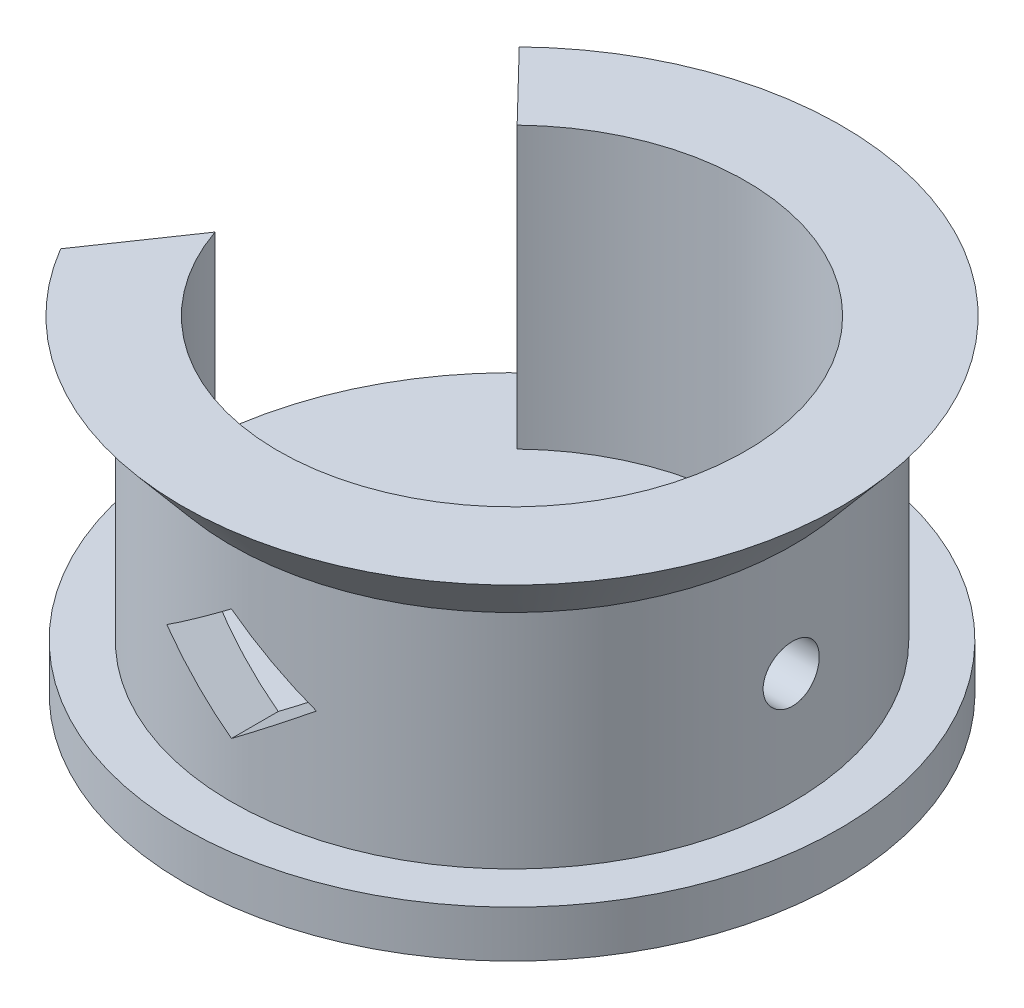
SolidWorks part; units mm, degrees
ref_plane "Front Plane" through (0, 0, 0) normal (0, 0, 1) x (1, 0, 0)
ref_plane "Top Plane" through (0, 0, 0) normal (0, 1, 0) x (1, 0, 0)
ref_plane "Right Plane" through (0, 0, 0) normal (1, 0, 0) x (0, 0, -1)
sketch "Sketch4" plane through (0, 0, 0) normal (0, 1, 0) x (1, 0, 0)
  circle A0 centre (0, 0) radius 7
extrude "Boss-Extrude3" add sketch "Sketch4" along normal blind 1
sketch "Sketch5" plane through (0, 1, 0) normal (0, 1, 0) x (1, 0, 0)
  circle A0 centre (0, 0) radius 6
  circle A1 centre (0, 0) radius 5
extrude "Boss-Extrude4" add sketch "Sketch5" along normal blind 4.75
sketch "Sketch6" plane through (0, 0, 0) normal (0, 0, 1) x (1, 0, 0)
  line L0 (0, 5.75) -> (6, 5.75)
  line L1 (5, 5.75) -> (-5, 5.75) construction
  line L7 (6, 7) -> (6, 5.75)
  line L8 (0, 7) -> (6, 7)
  line L10 (0, 5.75) -> (0, 7)
revolve "Revolve4" add sketch "Sketch6" angle 360 about L10
sketch "Sketch9" plane through (0, 7, 0) normal (0, 1, 0) x (1, 0, 0)
  circle A0 centre (0, 0) radius 5
extrude "Cut-Extrude3" cut sketch "Sketch9" against normal blind 3
sketch "Sketch11" plane through (0, 0, 0) normal (0, 0, 1) x (1, 0, 0)
  line L0 (0, 3.375) -> (0, 4.575)
  line L1 (0, 3.375) -> (0, 2.175)
  line L2 (0, 3.375) -> (-1.2, 3.375)
  line L3 (0, 3.375) -> (1.2, 3.375)
  line L5 (0, 2.175) -> (1.6, 3.375)
  line L6 (0, 4.575) -> (1.6, 3.375)
  line L7 (0, 3.375) -> (-1.6, 3.375)
  line L8 (-1.6, 3.375) -> (0, 4.575)
  line L9 (-1.6, 3.375) -> (0, 2.175)
  line L15 (0, 3.375) -> (1.6, 3.375)
extrude "Cut-Extrude7" cut sketch "Sketch11" along normal blind 10 contours L3 L15 L6 L0 | L8 L7 L2 L0 | L7 L9 L1 L2 | L15 L3 L1 L5 region at (-0.5333, 3.775, 0) region at (0.5333, 2.975, 0) region at (-0.5333, 2.975, 0) region at (0.5333, 3.775, 0)
sketch "Sketch12" plane through (0, 0, 0) normal (1, 0, 0) x (0, 0, -1)
  line L1 (6, 7) -> (-6, 7) construction
  line L5 (-6, 7) -> (-6, 5.75)
  line L6 (-6, 7) -> (-6, 4.575) construction
  line L7 (0, 7) -> (0, 8.25)
  line L8 (-7.0489, 7) -> (-6, 5.75)
  line L9 (-7.0489, 7) -> (-6, 7)
  line L10 (-7.0489, 7) -> (-6, 7)
revolve "Revolve8" add sketch "Sketch12" angle 360 about L7 region at (0, 6.5833, 6.3496)
sketch "Sketch13" plane through (0, 1, 0) normal (0, 1, 0) x (1, 0, 0)
  circle A0 centre (0, 0) radius 2.4
extrude "Cut-Extrude8" cut sketch "Sketch13" against normal blind 10
sketch "Sketch14" plane through (0, 7, 0) normal (0, 1, 0) x (1, 0, 0)
  line L0 (-4.73, -1.6207) -> (-6.071, -3.5819)
  line L1 (-3.4803, 3.5899) -> (-4.9065, 5.0609)
  circle A0 centre (0, 0) radius 5 construction
  circle A1 centre (0, 0) radius 7.0489 construction
  circle A2 centre (0, 0) radius 5 construction
  circle A3 centre (0, 0) radius 5
  circle A4 centre (0, 0) radius 7.0489
  circle M3 centre (0, 0) radius 5
  circle M4 centre (0, 0) radius 7.0489
extrude "Cut-Extrude9" cut sketch "Sketch14" against normal blind 6 contours L1 L0 M3 M4 region at (-5.6269, 7, -0.9729)
sketch "Sketch15" plane through (0, 0, 0) normal (1, 0, 0) x (0, 0, -1)
  line L0 (0, 1) -> (0, 5.75)
  line L1 (6, 1) -> (-6, 1) construction
  line L2 (-6, 5.75) -> (6, 5.75) construction
  circle A0 centre (0, 3.375) radius 0.6
extrude "Cut-Extrude10" cut sketch "Sketch15" along normal blind 10 contours L0 A0 | L0 A0 region at (0, 3.375, 0.2546) region at (0, 3.375, -0.2546)
